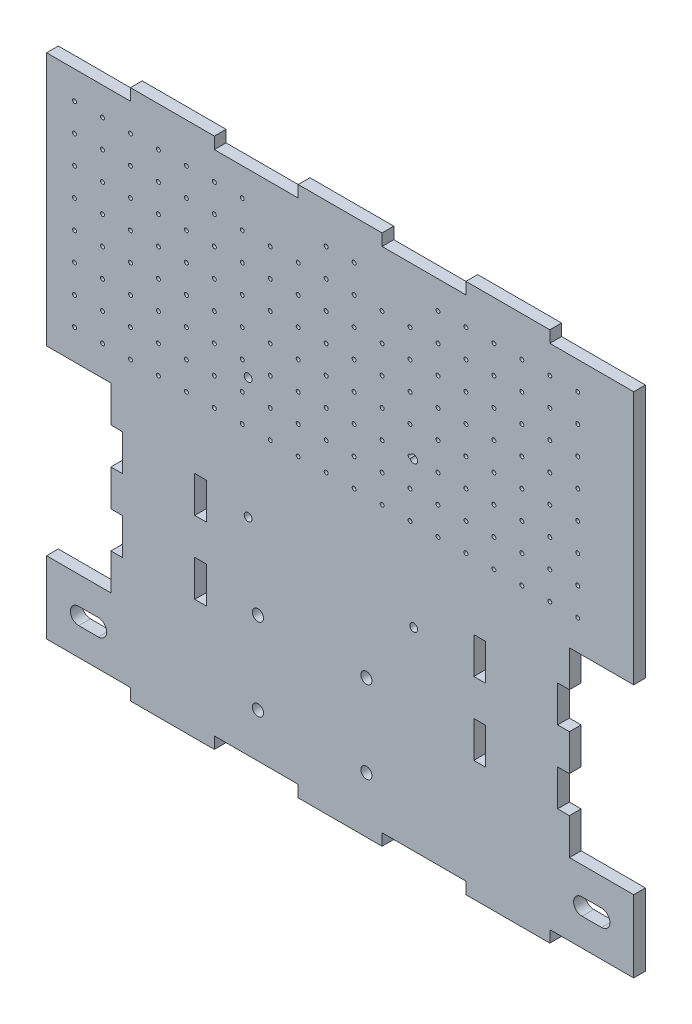
SolidWorks part; units mm, degrees
ref_plane "Front Plane" through (0, 0, 0) normal (0, 0, 1) x (1, 0, 0)
ref_plane "Top Plane" through (0, 0, 0) normal (0, 1, 0) x (1, 0, 0)
ref_plane "Right Plane" through (0, 0, 0) normal (1, 0, 0) x (0, 0, -1)
sketch "Sketch1" plane through (0, 0, 0) normal (0, 0, 1) x (1, 0, 0)
  line L1 (-133.35, 120.65) -> (133.35, 120.65)
  line L2 (-133.35, 120.65) -> (-133.35, -120.65)
  line L3 (-133.35, -120.65) -> (133.35, -120.65)
  line L4 (133.35, 120.65) -> (133.35, -120.65)
  line L5 (-133.35, 120.65) -> (133.35, -120.65) construction
  line L6 (-133.35, -120.65) -> (133.35, 120.65) construction
  point P0 (0, 0)
  dimension "D1" = 241.3
  dimension "D2" = 266.7
extrude "Boss-Extrude1" add sketch "Sketch1" along normal blind 5.334
sketch "Sketch2" plane through (0, 0, 0) normal (0, 0, -1) x (-1, 0, 0)
  line L0 (133.35, 120.65) -> (133.35, -120.65) construction
  line L1 (133.35, 0) -> (104.14, 0)
  line L2 (133.35, 0) -> (133.35, -82.55)
  line L3 (133.35, -82.55) -> (104.14, -82.55)
  line L4 (104.14, 0) -> (104.14, -82.55)
  line L5 (-133.35, -120.65) -> (-133.35, 120.65) construction
  line L6 (-133.35, 0) -> (-104.14, 0)
  line L7 (-133.35, 0) -> (-133.35, -82.55)
  line L8 (-133.35, -82.55) -> (-104.14, -82.55)
  line L9 (-104.14, 0) -> (-104.14, -82.55)
  line L10 (133.35, -120.65) -> (-133.35, -120.65) construction
  dimension "D1" = 82.55
  dimension "D2" = 82.55
  dimension "D3" = 38.1
  dimension "D4" = 38.1
  dimension "D5" = 29.21
  dimension "D6" = 29.21
extrude "Cut-Extrude1" cut sketch "Sketch2" against normal through all
sketch "Sketch9" plane through (0, 0, 5.334) normal (0, 0, 1) x (1, 0, 0)
  line L0 (-104.14, 0) -> (-104.14, -82.55) construction
  line L1 (-104.14, -16.51) -> (-98.806, -16.51)
  line L2 (-104.14, -16.51) -> (-104.14, -33.02)
  line L3 (-104.14, -33.02) -> (-98.806, -33.02)
  line L4 (-98.806, -16.51) -> (-98.806, -33.02)
  line L5 (-104.14, 0) -> (-98.806, 0) construction
  line L6 (-104.14, -49.53) -> (-98.806, -49.53)
  line L7 (-104.14, -49.53) -> (-104.14, -66.04)
  line L8 (-104.14, -66.04) -> (-98.806, -66.04)
  line L9 (-98.806, -49.53) -> (-98.806, -66.04)
  line L10 (-98.806, 0) -> (-98.806, -16.51) construction
  line L11 (-98.806, -33.02) -> (-98.806, -49.53) construction
  line L12 (-104.14, -82.55) -> (-98.806, -82.55) construction
  line L13 (-98.806, -82.55) -> (-98.806, -66.04) construction
  line L14 (0, -120.65) -> (0, 120.65) construction
  line L15 (-133.35, -120.65) -> (133.35, -120.65) construction
  line L16 (133.35, 120.65) -> (-133.35, 120.65) construction
  line L17 (98.806, -82.55) -> (98.806, -66.04) construction
  line L18 (104.14, -82.55) -> (98.806, -82.55) construction
  line L19 (98.806, -33.02) -> (98.806, -49.53) construction
  line L20 (98.806, 0) -> (98.806, -16.51) construction
  line L21 (104.14, 0) -> (98.806, 0) construction
  line L22 (98.806, -49.53) -> (98.806, -66.04)
  line L23 (104.14, -66.04) -> (98.806, -66.04)
  line L24 (104.14, -49.53) -> (104.14, -66.04)
  line L25 (104.14, -49.53) -> (98.806, -49.53)
  line L26 (98.806, -16.51) -> (98.806, -33.02)
  line L27 (104.14, -33.02) -> (98.806, -33.02)
  line L28 (104.14, -16.51) -> (104.14, -33.02)
  line L29 (104.14, -16.51) -> (98.806, -16.51)
  dimension "D1" = 5.334
extrude "Cut-Extrude2" cut sketch "Sketch9" against normal through all
sketch "Sketch10" plane through (0, 0, 5.334) normal (0, 0, 1) x (1, 0, 0)
  line L2 (-133.35, -120.65) -> (133.35, -120.65) construction
  line L3 (-133.35, -82.55) -> (-133.35, -120.65) construction
  circle A0 centre (-37.338, -95.25) radius 2.54
  circle A1 centre (11.938, -95.25) radius 2.54
  circle A2 centre (11.938, -57.912) radius 2.54
  circle A3 centre (-37.338, -57.912) radius 2.54
  dimension "D1" = 96.012
  dimension "D2" = 49.276
  dimension "D3" = 25.4
  dimension "D4" = 2
  dimension "D5" = 2
extrude "Cut-Extrude3" cut sketch "Sketch10" against normal through all
sketch "Sketch23" plane through (0, 0, 5.334) normal (0, 0, 1) x (1, 0, 0)
  line L0 (-98.806, -24.765) -> (-61.976, -24.765) construction
  line L1 (-98.806, -33.02) -> (-98.806, -16.51) construction
  line L2 (-98.806, -16.51) -> (-60.706, -16.51) construction
  line L3 (-98.806, -33.02) -> (-60.706, -33.02) construction
  line L4 (-104.14, -41.275) -> (104.14, -41.275) construction
  line L5 (-104.14, -33.02) -> (-104.14, -49.53) construction
  line L6 (104.14, -49.53) -> (104.14, -33.02) construction
  line L7 (-98.806, -49.53) -> (-60.706, -49.53) construction
  line L8 (-98.806, -57.785) -> (-61.976, -57.785) construction
  line L9 (-98.806, -66.04) -> (-60.706, -66.04) construction
  line L10 (0, -120.65) -> (0, 120.65) construction
  line L11 (-133.35, -120.65) -> (133.35, -120.65) construction
  line L12 (133.35, 120.65) -> (-133.35, 120.65) construction
  line L13 (98.806, -66.04) -> (60.706, -66.04) construction
  line L14 (98.806, -49.53) -> (60.706, -49.53) construction
  line L15 (98.806, -33.02) -> (60.706, -33.02) construction
  line L16 (98.806, -16.51) -> (60.706, -16.51) construction
  line L17 (-60.706, -66.04) -> (-66.04, -66.04)
  line L18 (60.706, -16.51) -> (66.04, -16.51)
  line L19 (60.706, -16.51) -> (60.706, -33.02)
  line L20 (60.706, -33.02) -> (66.04, -33.02)
  line L21 (66.04, -16.51) -> (66.04, -33.02)
  line L22 (60.706, -49.53) -> (66.04, -49.53)
  line L23 (60.706, -49.53) -> (60.706, -66.04)
  line L24 (60.706, -66.04) -> (66.04, -66.04)
  line L25 (66.04, -49.53) -> (66.04, -66.04)
  line L26 (-66.04, -49.53) -> (-66.04, -66.04)
  line L27 (-60.706, -49.53) -> (-60.706, -66.04)
  line L28 (-60.706, -49.53) -> (-66.04, -49.53)
  line L29 (-60.706, -33.02) -> (-66.04, -33.02)
  line L30 (-66.04, -16.51) -> (-66.04, -33.02)
  line L31 (-60.706, -16.51) -> (-66.04, -16.51)
  line L32 (-60.706, -16.51) -> (-60.706, -33.02)
  line L33 (98.806, -16.51) -> (98.806, -33.02) construction
  dimension "D1" = 5.334
  dimension "D2" = 5.334
  dimension "D3" = 32.766
  dimension "D4" = 32.766
extrude "Cut-Extrude8" cut sketch "Sketch23" against normal through all
sketch "Sketch28" plane through (0, 0, 0) normal (0, 0, -1) x (-1, 0, 0)
  line L0 (133.35, -120.65) -> (-133.35, -120.65) construction
  line L1 (-133.35, -120.65) -> (-95.25, -120.65)
  line L2 (-133.35, -120.65) -> (-133.35, -115.316)
  line L3 (-133.35, -115.316) -> (-95.25, -115.316)
  line L4 (-95.25, -120.65) -> (-95.25, -115.316)
  line L5 (-57.15, -120.65) -> (-19.05, -120.65)
  line L6 (-57.15, -120.65) -> (-57.15, -115.316)
  line L7 (-57.15, -115.316) -> (-19.05, -115.316)
  line L8 (-19.05, -120.65) -> (-19.05, -115.316)
  line L9 (133.35, -82.55) -> (133.35, -120.65) construction
  line L10 (19.05, -120.65) -> (57.15, -120.65)
  line L11 (19.05, -120.65) -> (19.05, -115.316)
  line L12 (19.05, -115.316) -> (57.15, -115.316)
  line L13 (57.15, -120.65) -> (57.15, -115.316)
  line L14 (95.25, -120.65) -> (133.35, -120.65)
  line L16 (95.25, -115.316) -> (133.35, -115.316)
  line L17 (133.35, -120.65) -> (133.35, -115.316)
  line L18 (-95.25, -115.316) -> (-57.15, -115.316) construction
  line L19 (-19.05, -115.316) -> (19.05, -115.316) construction
  line L20 (95.25, -115.316) -> (57.15, -115.316) construction
  line L21 (133.35, 120.65) -> (133.35, -115.316) construction
  line L22 (133.35, -115.316) -> (133.5431, -115.1744) construction
  line L41 (95.25, -120.65) -> (95.25, -115.316)
  dimension "D1" = 5.334
extrude "Cut-Extrude13" cut sketch "Sketch28" against normal through all
sketch "Sketch29" plane through (0, 0, 0) normal (0, 0, -1) x (-1, 0, 0)
  line L0 (-133.35, 120.65) -> (133.35, 120.65) construction
  line L1 (-133.35, 120.65) -> (-95.25, 120.65)
  line L2 (-133.35, 120.65) -> (-133.35, 115.316)
  line L3 (-133.35, 115.316) -> (-95.25, 115.316)
  line L4 (-95.25, 120.65) -> (-95.25, 115.316)
  line L5 (-57.15, 120.65) -> (-19.05, 120.65)
  line L6 (-57.15, 120.65) -> (-57.15, 115.316)
  line L7 (-57.15, 115.316) -> (-19.05, 115.316)
  line L8 (-19.05, 120.65) -> (-19.05, 115.316)
  line L9 (133.35, 120.65) -> (133.35, 0) construction
  line L10 (19.05, 120.65) -> (57.15, 120.65)
  line L11 (19.05, 120.65) -> (19.05, 115.316)
  line L12 (19.05, 115.316) -> (57.15, 115.316)
  line L13 (57.15, 120.65) -> (57.15, 115.316)
  line L14 (95.25, 120.65) -> (133.35, 120.65)
  line L15 (95.25, 120.65) -> (95.25, 115.316)
  line L16 (95.25, 115.316) -> (133.35, 115.316)
  line L17 (133.35, 120.65) -> (133.35, 115.316)
  line L18 (-95.25, 115.316) -> (-57.15, 115.316) construction
  line L19 (19.05, 115.316) -> (-19.05, 115.316) construction
  line L20 (57.15, 115.316) -> (95.25, 115.316) construction
  dimension "D1" = 5.334
extrude "Cut-Extrude14" cut sketch "Sketch29" against normal through all
sketch "Sketch30" plane through (0, 0, 5.334) normal (0, 0, 1) x (1, 0, 0)
  line L0 (-95.25, 115.316) -> (-133.35, 115.316) construction
  line L1 (-133.35, 115.316) -> (-133.35, 0) construction
  line L2 (-120.65, 102.616) -> (-107.95, 102.616) construction
  circle A0 centre (-120.65, 102.616) radius 0.889
  circle A1 centre (-107.95, 102.616) radius 0.889
  circle A2 centre (-95.25, 102.616) radius 0.889
  circle A3 centre (-82.55, 102.616) radius 0.889
  circle A4 centre (-69.85, 102.616) radius 0.889
  circle A5 centre (-57.15, 102.616) radius 0.889
  circle A6 centre (-44.45, 102.616) radius 0.889
  circle A7 centre (-31.75, 102.616) radius 0.889 [skipped]
  circle A8 centre (-19.05, 102.616) radius 0.889 [skipped]
  circle A9 centre (-6.35, 102.616) radius 0.889
  circle A10 centre (6.35, 102.616) radius 0.889
  circle A11 centre (19.05, 102.616) radius 0.889 [skipped]
  circle A12 centre (31.75, 102.616) radius 0.889 [skipped]
  circle A13 centre (44.45, 102.616) radius 0.889
  circle A14 centre (57.15, 102.616) radius 0.889
  circle A15 centre (69.85, 102.616) radius 0.889
  circle A16 centre (82.55, 102.616) radius 0.889
  circle A17 centre (95.25, 102.616) radius 0.889
  circle A18 centre (107.95, 102.616) radius 0.889
  circle A19 centre (-107.95, 89.916) radius 0.889
  circle A20 centre (-95.25, 89.916) radius 0.889
  circle A21 centre (-82.55, 89.916) radius 0.889
  circle A22 centre (-69.85, 89.916) radius 0.889
  circle A23 centre (-57.15, 89.916) radius 0.889
  circle A24 centre (-44.45, 89.916) radius 0.889
  circle A25 centre (-31.75, 89.916) radius 0.889
  circle A26 centre (-19.05, 89.916) radius 0.889
  circle A27 centre (-6.35, 89.916) radius 0.889
  circle A28 centre (6.35, 89.916) radius 0.889
  circle A29 centre (19.05, 89.916) radius 0.889
  circle A30 centre (31.75, 89.916) radius 0.889
  circle A31 centre (44.45, 89.916) radius 0.889
  circle A32 centre (57.15, 89.916) radius 0.889
  circle A33 centre (69.85, 89.916) radius 0.889
  circle A34 centre (82.55, 89.916) radius 0.889
  circle A35 centre (95.25, 89.916) radius 0.889
  circle A36 centre (107.95, 89.916) radius 0.889
  circle A37 centre (-107.95, 77.216) radius 0.889
  circle A38 centre (-95.25, 77.216) radius 0.889
  circle A39 centre (-82.55, 77.216) radius 0.889
  circle A40 centre (-69.85, 77.216) radius 0.889
  circle A41 centre (-57.15, 77.216) radius 0.889
  circle A42 centre (-44.45, 77.216) radius 0.889
  circle A43 centre (-31.75, 77.216) radius 0.889
  circle A44 centre (-19.05, 77.216) radius 0.889
  circle A45 centre (-6.35, 77.216) radius 0.889
  circle A46 centre (6.35, 77.216) radius 0.889
  circle A47 centre (19.05, 77.216) radius 0.889
  circle A48 centre (31.75, 77.216) radius 0.889
  circle A49 centre (44.45, 77.216) radius 0.889
  circle A50 centre (57.15, 77.216) radius 0.889
  circle A51 centre (69.85, 77.216) radius 0.889
  circle A52 centre (82.55, 77.216) radius 0.889
  circle A53 centre (95.25, 77.216) radius 0.889
  circle A54 centre (107.95, 77.216) radius 0.889
  circle A55 centre (-107.95, 64.516) radius 0.889
  circle A56 centre (-95.25, 64.516) radius 0.889
  circle A57 centre (-82.55, 64.516) radius 0.889
  circle A58 centre (-69.85, 64.516) radius 0.889
  circle A59 centre (-57.15, 64.516) radius 0.889
  circle A60 centre (-44.45, 64.516) radius 0.889
  circle A61 centre (-31.75, 64.516) radius 0.889
  circle A62 centre (-19.05, 64.516) radius 0.889
  circle A63 centre (-6.35, 64.516) radius 0.889
  circle A64 centre (6.35, 64.516) radius 0.889
  circle A65 centre (19.05, 64.516) radius 0.889
  circle A66 centre (31.75, 64.516) radius 0.889
  circle A67 centre (44.45, 64.516) radius 0.889
  circle A68 centre (57.15, 64.516) radius 0.889
  circle A69 centre (69.85, 64.516) radius 0.889
  circle A70 centre (82.55, 64.516) radius 0.889
  circle A71 centre (95.25, 64.516) radius 0.889
  circle A72 centre (107.95, 64.516) radius 0.889
  circle A73 centre (-107.95, 51.816) radius 0.889
  circle A74 centre (-95.25, 51.816) radius 0.889
  circle A75 centre (-82.55, 51.816) radius 0.889
  circle A76 centre (-69.85, 51.816) radius 0.889
  circle A77 centre (-57.15, 51.816) radius 0.889
  circle A78 centre (-44.45, 51.816) radius 0.889
  circle A79 centre (-31.75, 51.816) radius 0.889
  circle A80 centre (-19.05, 51.816) radius 0.889
  circle A81 centre (-6.35, 51.816) radius 0.889
  circle A82 centre (6.35, 51.816) radius 0.889
  circle A83 centre (19.05, 51.816) radius 0.889
  circle A84 centre (31.75, 51.816) radius 0.889
  circle A85 centre (44.45, 51.816) radius 0.889
  circle A86 centre (57.15, 51.816) radius 0.889
  circle A87 centre (69.85, 51.816) radius 0.889
  circle A88 centre (82.55, 51.816) radius 0.889
  circle A89 centre (95.25, 51.816) radius 0.889
  circle A90 centre (107.95, 51.816) radius 0.889
  circle A91 centre (-107.95, 39.116) radius 0.889
  circle A92 centre (-95.25, 39.116) radius 0.889
  circle A93 centre (-82.55, 39.116) radius 0.889
  circle A94 centre (-69.85, 39.116) radius 0.889
  circle A95 centre (-57.15, 39.116) radius 0.889
  circle A96 centre (-44.45, 39.116) radius 0.889
  circle A97 centre (-31.75, 39.116) radius 0.889
  circle A98 centre (-19.05, 39.116) radius 0.889
  circle A99 centre (-6.35, 39.116) radius 0.889
  circle A100 centre (6.35, 39.116) radius 0.889
  circle A101 centre (19.05, 39.116) radius 0.889
  circle A102 centre (31.75, 39.116) radius 0.889
  circle A103 centre (44.45, 39.116) radius 0.889
  circle A104 centre (57.15, 39.116) radius 0.889
  circle A105 centre (69.85, 39.116) radius 0.889
  circle A106 centre (82.55, 39.116) radius 0.889
  circle A107 centre (95.25, 39.116) radius 0.889
  circle A108 centre (107.95, 39.116) radius 0.889
  circle A109 centre (-107.95, 26.416) radius 0.889
  circle A110 centre (-95.25, 26.416) radius 0.889
  circle A111 centre (-82.55, 26.416) radius 0.889
  circle A112 centre (-69.85, 26.416) radius 0.889
  circle A113 centre (-57.15, 26.416) radius 0.889
  circle A114 centre (-44.45, 26.416) radius 0.889
  circle A115 centre (-31.75, 26.416) radius 0.889
  circle A116 centre (-19.05, 26.416) radius 0.889
  circle A117 centre (-6.35, 26.416) radius 0.889
  circle A118 centre (6.35, 26.416) radius 0.889
  circle A119 centre (19.05, 26.416) radius 0.889
  circle A120 centre (31.75, 26.416) radius 0.889
  circle A121 centre (44.45, 26.416) radius 0.889
  circle A122 centre (57.15, 26.416) radius 0.889
  circle A123 centre (69.85, 26.416) radius 0.889
  circle A124 centre (82.55, 26.416) radius 0.889
  circle A125 centre (95.25, 26.416) radius 0.889
  circle A126 centre (107.95, 26.416) radius 0.889
  circle A127 centre (-107.95, 13.716) radius 0.889
  circle A128 centre (-95.25, 13.716) radius 0.889
  circle A129 centre (-82.55, 13.716) radius 0.889
  circle A130 centre (-69.85, 13.716) radius 0.889
  circle A131 centre (-57.15, 13.716) radius 0.889
  circle A132 centre (-44.45, 13.716) radius 0.889
  circle A133 centre (-31.75, 13.716) radius 0.889
  circle A134 centre (-19.05, 13.716) radius 0.889
  circle A135 centre (-6.35, 13.716) radius 0.889
  circle A136 centre (6.35, 13.716) radius 0.889
  circle A137 centre (19.05, 13.716) radius 0.889
  circle A138 centre (31.75, 13.716) radius 0.889
  circle A139 centre (44.45, 13.716) radius 0.889
  circle A140 centre (57.15, 13.716) radius 0.889
  circle A141 centre (69.85, 13.716) radius 0.889
  circle A142 centre (82.55, 13.716) radius 0.889
  circle A143 centre (95.25, 13.716) radius 0.889
  circle A144 centre (107.95, 13.716) radius 0.889
  circle A145 centre (-120.65, 89.916) radius 0.889
  circle A146 centre (-120.65, 77.216) radius 0.889
  circle A147 centre (-120.65, 64.516) radius 0.889
  circle A148 centre (-120.65, 51.816) radius 0.889
  circle A149 centre (-120.65, 39.116) radius 0.889
  circle A150 centre (-120.65, 26.416) radius 0.889
  circle A151 centre (-120.65, 13.716) radius 0.889
  dimension "D1" = 1.778
  dimension "D2" = 12.7
  dimension "D3" = 12.7
  dimension "D6" = 12.7
  dimension "D4" = 19
  dimension "D5" = 8
extrude "Cut-Extrude15" cut sketch "Sketch30" against normal through all
sketch "Sketch32" plane through (0, 0, 0) normal (0, 0, -1) x (-1, 0, 0)
  circle A0 centre (-33.4037, -27.3887) radius 1.778 construction
  circle A1 centre (41.7803, -21.5467) radius 1.778 construction
  circle A2 centre (-33.4037, 38.9053) radius 1.778 construction
  circle A3 centre (41.7803, 33.3173) radius 1.778 construction
  circle A4 centre (-33.4037, -27.3887) radius 1.778
  circle A5 centre (41.7803, -21.5467) radius 1.778
  circle A6 centre (-33.4037, 38.9053) radius 1.778
  circle A7 centre (41.7803, 33.3173) radius 1.778
extrude "Cut-Extrude16" cut sketch "Sketch32" against normal through all
sketch "Sketch35" plane through (0, 0, 5.334) normal (0, 0, 1) x (1, 0, 0)
  line L0 (0, 120.65) -> (0, -120.65) construction
  line L1 (19.05, 120.65) -> (-19.05, 120.65) construction
  line L2 (-19.05, -120.65) -> (19.05, -120.65) construction
  line L3 (-133.35, -98.933) -> (133.35, -98.933) construction
  line L4 (-133.35, -82.55) -> (-133.35, -115.316) construction
  line L5 (133.35, -115.316) -> (133.35, -82.55) construction
  line L6 (-118.745, -82.55) -> (-118.745, -115.316) construction
  line L7 (-104.14, -82.55) -> (-133.35, -82.55) construction
  line L8 (-133.35, -115.316) -> (-95.25, -115.316) construction
  line L9 (-114.3, -115.316) -> (-114.3, -82.55) construction
  line L10 (118.745, -82.55) -> (118.745, -115.316) construction
  line L11 (133.35, -82.55) -> (104.14, -82.55) construction
  line L12 (95.25, -115.316) -> (133.35, -115.316) construction
  line L13 (114.3, -115.316) -> (114.3, -82.55) construction
  line L14 (-109.855, -98.933) -> (-118.745, -98.933) construction
  line L15 (-109.855, -102.743) -> (-118.745, -102.743)
  line L16 (-109.855, -95.123) -> (-118.745, -95.123)
  line L17 (109.855, -98.933) -> (118.745, -98.933) construction
  line L18 (109.855, -95.123) -> (118.745, -95.123)
  line L19 (109.855, -102.743) -> (118.745, -102.743)
  arc A0 (-109.855, -102.743) -> (-109.855, -95.123) centre (-109.855, -98.933) ccw
  arc A1 (-118.745, -95.123) -> (-118.745, -102.743) centre (-118.745, -98.933) ccw
  arc A2 (109.855, -95.123) -> (109.855, -102.743) centre (109.855, -98.933) ccw
  arc A3 (118.745, -102.743) -> (118.745, -95.123) centre (118.745, -98.933) ccw
  point P30 (-114.3, -98.933)
  point P36 (114.3, -98.933)
extrude "Cut-Extrude19" cut sketch "Sketch35" against normal through all
equation "\"MDF\"= .21in"
equation "\"Foamcore\"= .13in"
equation "\"Gmaterial\"= \"MDF\""
equation "\"D1@Sketch9\"=\"MDF\""
equation "\"D1@Sketch23\"=\"MDF\""
equation "\"D2@Sketch23\"=\"D1@Sketch23\""
equation "\"D1@Boss-Extrude1\"=\"MDF\""
equation "\"D3@Sketch23\"=1.29"
equation "\"D1@Sketch28\"=\"MDF\""
equation "\"D1@Sketch29\"=\"MDF\""
